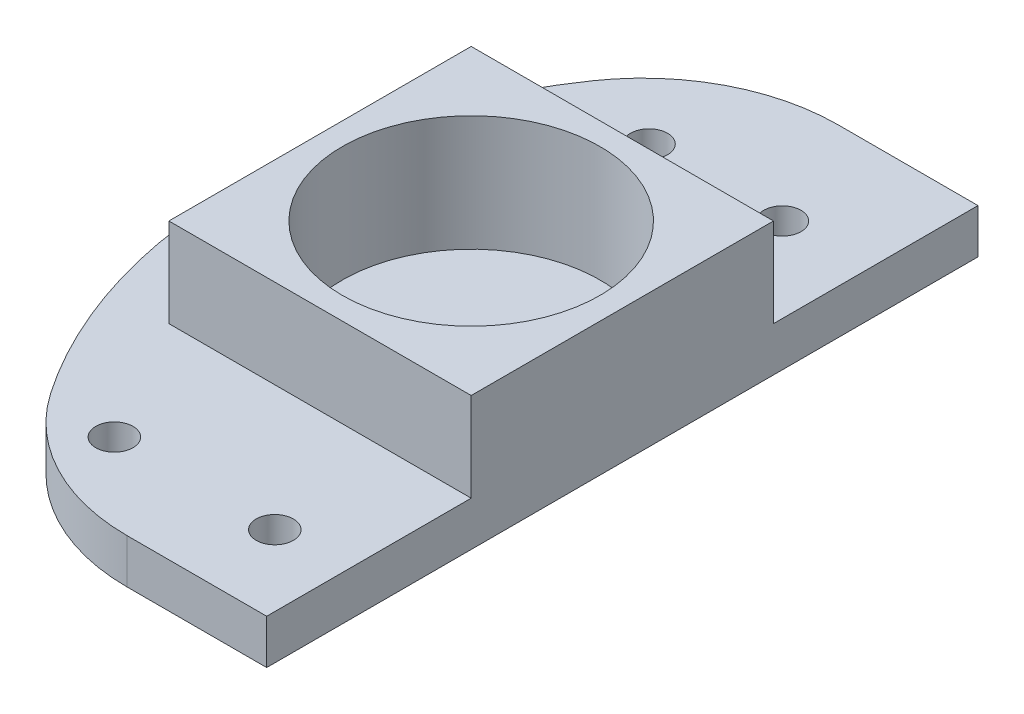
SolidWorks part; units mm, degrees
ref_plane "Front Plane" through (0, 0, 0) normal (0, 0, 1) x (1, 0, 0)
ref_plane "Top Plane" through (0, 0, 0) normal (0, 1, 0) x (1, 0, 0)
ref_plane "Right Plane" through (0, 0, 0) normal (1, 0, 0) x (0, 0, -1)
sketch "Sketch2" plane through (0, 0, 0) normal (0, 1, 0) x (1, 0, 0)
  line L1 (-57.15, -57.15) -> (57.15, -57.15)
  line L2 (-57.15, -57.15) -> (-57.15, 57.15)
  line L3 (-57.15, 57.15) -> (57.15, 57.15)
  line L4 (57.15, -57.15) -> (57.15, 57.15)
  line L5 (-57.15, -57.15) -> (57.15, 57.15) construction
  line L6 (-57.15, 57.15) -> (57.15, -57.15) construction
  circle A1 centre (0, 0) radius 57.15
  dimension "D1" = 114.3
extrude "Boss-Extrude1" add sketch "Sketch2" along normal blind 19.05 contours A1 L3 L2 | A1 | A1 L4 L3 | A1 L1 L4 | A1 L2 L1 region at (-44.3845, 0, 44.3845) region at (44.3845, 0, 44.3845) region at (0, 0, 0) region at (-44.3845, 0, -44.3845) region at (44.3845, 0, -44.3845)
sketch "Sketch3" plane through (0, 19.05, 0) normal (0, 1, 0) x (1, 0, 0)
  line L0 (-57.15, 57.15) -> (57.15, 57.15) construction
  line L2 (-21.59, -21.59) -> (21.59, -21.59)
  line L3 (-21.59, -21.59) -> (-21.59, 21.59)
  line L4 (-21.59, 21.59) -> (21.59, 21.59)
  line L5 (21.59, -21.59) -> (21.59, 21.59)
  line L6 (-21.59, -21.59) -> (21.59, 21.59) construction
  line L7 (-21.59, 21.59) -> (21.59, -21.59) construction
  circle A0 centre (0, 0) radius 18.415
  circle A1 centre (0, 0) radius 21.59
  circle A4 centre (0, 0) radius 57.15
  line M9 (-57.15, 57.15) -> (-57.15, -57.15)
  line M10 (-57.15, -57.15) -> (57.15, -57.15)
  line M11 (57.15, -57.15) -> (57.15, 57.15)
  line M12 (57.15, 57.15) -> (-57.15, 57.15)
  dimension "D1" = 36.83
  dimension "D2" = 3.175
extrude "Cut-Extrude1" cut sketch "Sketch3" against normal blind 16.51 contours A0
extrude "Cut-Extrude2" cut sketch "Sketch3<4>" against normal blind 12.7 contours A4 L5 L2 L3 L4 | A4 M9 M10 | A4 M12 M9 | A4 M11 M12 | A4 M10 M11 region at (39.2682, 19.05, 39.2682) region at (44.3845, 19.05, 44.3845) region at (44.3845, 19.05, -44.3845) region at (-44.3845, 19.05, -44.3845) region at (-44.3845, 19.05, 44.3845)
sketch "Sketch3<4>" plane through (0, 19.05, 0) normal (0, 1, 0) x (1, 0, 0) same geometry as "Sketch3"
sketch "Sketch5" plane through (0, 6.35, 0) normal (0, 1, 0) x (1, 0, 0)
  line L0 (57.15, 57.15) -> (-57.15, 57.15) construction
  line L5 (-21.59, -57.15) -> (21.59, -57.15)
  line L6 (-21.59, -57.15) -> (-21.59, 57.15)
  line L11 (-21.59, 57.15) -> (21.59, 57.15)
  line L12 (21.59, -57.15) -> (21.59, 57.15)
  line L13 (-21.59, -57.15) -> (21.59, 57.15) construction
  line L14 (-21.59, 57.15) -> (21.59, -57.15) construction
  line L15 (-21.59, -21.59) -> (-21.59, 21.59) construction
  line L16 (57.15, -57.15) -> (57.15, 57.15) construction
  line L17 (-57.15, -57.15) -> (57.15, -57.15) construction
  line L18 (-57.15, 57.15) -> (-57.15, -57.15) construction
  line L19 (57.15, -57.15) -> (57.15, 57.15)
  line L20 (-57.15, -57.15) -> (57.15, -57.15)
  line L21 (-57.15, 57.15) -> (-57.15, -57.15)
  line L22 (57.15, 57.15) -> (-57.15, 57.15)
  line L23 (21.59, 50.8) -> (-10.7675, 50.8)
  line L24 (21.59, -50.8) -> (-10.7675, -50.8)
  circle A0 centre (34.925, 0) radius 68.326
  point P0 (0, 0)
  line M34 (21.59, 21.59) -> (21.59, -21.59)
  line M38 (-57.15, 57.15) -> (-57.15, -57.15)
  line M39 (-57.15, -57.15) -> (57.15, -57.15)
  line M40 (57.15, -57.15) -> (57.15, 57.15)
  line M41 (57.15, 57.15) -> (-57.15, 57.15)
  dimension "D1" = 136.652
  dimension "D2" = 34.925
  dimension "D3" = 6.35
  dimension "D4" = 6.35
extrude "Cut-Extrude3" cut sketch "Sketch5" against normal blind 12.7 contours L12 M39 M40 M41 M34 | A0 L6 M41 M38 M39 | A0 L22 L6 | A0 L6 M39 | A0 L23 L12 M41 | L24 A0 L20 L12 region at (-15.6611, 6.35, 51.3177) region at (-41.6955, 6.35, 0) region at (7.265, 6.35, 53.8221) region at (39.37, 6.35, 0) region at (-15.6611, 6.35, -51.3177) region at (7.265, 6.35, -53.8221)
sketch "Sketch6" plane through (0, 6.35, 0) normal (0, 1, 0) x (1, 0, 0)
  line L0 (-18.415, 0) -> (21.59, 0) construction
  line L1 (0, 21.59) -> (0, -18.415) construction
  line L2 (-21.59, 21.59) -> (21.59, 21.59) construction
  line L3 (21.59, -21.59) -> (21.59, 21.59) construction
  circle A0 centre (0, 0) radius 18.415 construction
  circle A1 centre (0, -3.175) radius 38.1 construction
  point P4 (-11.4569, -39.5116)
  point P5 (11.4569, -39.5116)
  point P9 (-9.525, 34.925)
  point P10 (9.525, 34.925)
  point P11 (0, 0)
  point P17 (0, 0)
  point P20 (0, 0)
  point P23 (0, 0)
  point P24 (0, 0)
  point P25 (0, 0)
  dimension "D1" = 76.2
  dimension "D2" = 35
  dimension "D3" = 3.175
  dimension "D4" = 19.05
  dimension "D5" = 34.925
fillet "Fillet1" radius 27.94 2 edges at (-10.7675, 3.175, -50.8) (-10.7675, 3.175, 50.8)
hole_wizard "#4 (0.209) Diameter Hole1" positions "Sketch9" profile "Sketch8" hole size "#4" standard "ANSI Inch" end condition up to next
sketch "Sketch9" plane through (0, 6.35, 0) normal (0, 1, 0) x (1, 0, 0)
  point P0 (-9.525, 34.925)
  point P3 (9.525, 34.925)
  point P6 (11.4569, -39.5116)
  point P9 (-11.4569, -39.5116)
sketch "Sketch8" plane through (-9.525, 6.35, -34.925) normal (1, 0, 0) x (0, 0, 1)
  line L0 (0, 0) -> (0, 6.35)
  line L1 (0, 6.35) -> (2.6543, 6.35)
  line L2 (2.6543, 6.35) -> (2.6543, 0)
  line L5 (2.6543, 0) -> (0, 0)
  line L11 (0, -6.35) -> (0, 107.95) construction
  dimension "Thru Hole Dia." = 5.3086
  dimension "Thru Hole Depth" = 6.35
